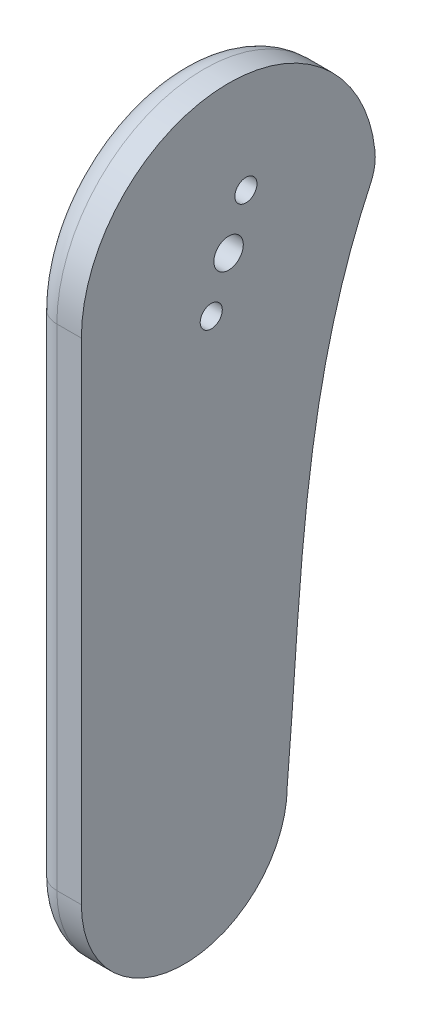
SolidWorks part; units mm, degrees
ref_plane "Front Plane" through (0, 0, 0) normal (0, 0, 1) x (1, 0, 0)
ref_plane "Top Plane" through (0, 0, 0) normal (0, 1, 0) x (1, 0, 0)
ref_plane "Right Plane" through (0, 0, 0) normal (1, 0, 0) x (0, 0, -1)
sketch "Sketch2" plane through (0, 0, 0) normal (1, 0, 0) x (0, 0, -1)
  line L2 (-30, 50) -> (-30, -50)
  arc A0 (-30, 50) -> (29.8379, 53.1141) centre (0, 50) cw
  arc A1 (29.8379, 53.1141) -> (28.9342, 47.8054) centre (19.892, 52.076) cw
  arc A2 (-30, -50) -> (11.9583, -50) centre (-9.0209, -50) ccw
  spline S0 degree 3 poles (28.9342, 47.8054) (24.8825, 39.2268) (14.6324, 7.562) (14.0777, -26.4513) (11.9583, -50) knots 0.023515 0.023515 0.023515 0.023515 0.298368 1 1 1 1
extrude "Boss-Extrude1" add sketch "Sketch2" along normal blind 10
fillet "Fillet1" radius 5 5 edges at (0, 50.3978, -29.7501) (0, 79.9595, 1.5591) (0, -70.9791, 9.0209) (0, 0, 30)
sketch "Sketch3" plane through (10, 0, 0) normal (1, 0, 0) x (0, 0, -1)
  circle A0 centre (0, 50) radius 3
  circle A1 centre (3.5323, 59.3554) radius 2.2528
  circle A2 centre (-3.5323, 40.6446) radius 2.25
extrude "Cut-Extrude2" cut sketch "Sketch3" against normal blind 5
